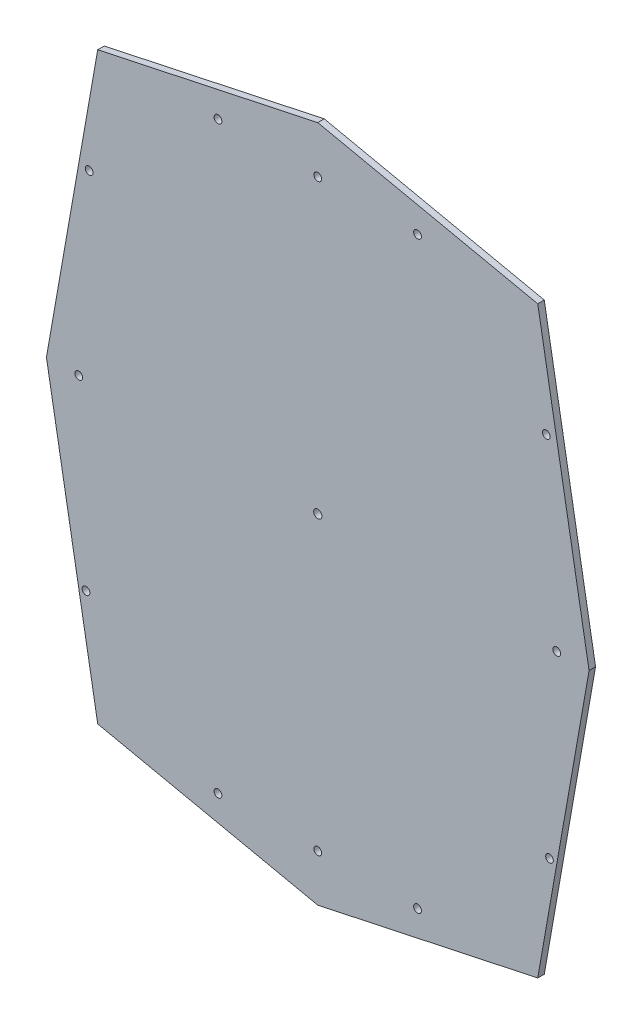
SolidWorks part; units mm, degrees
ref_plane "Front Plane" through (0, 0, 0) normal (0, 0, 1) x (1, 0, 0)
ref_plane "Top Plane" through (0, 0, 0) normal (0, 1, 0) x (1, 0, 0)
ref_plane "Right Plane" through (0, 0, 0) normal (1, 0, 0) x (0, 0, -1)
sketch "Sketch1" plane through (0, 0, -617.8603) normal (0, 0, 1) x (1, 0, 0)
  line L0 (-107.5, 142.6399) -> (-132.5632, 0)
  line L10 (-107.5, -142.6399) -> (-132.5632, 0)
  line L13 (0, 188.5) -> (0, 142.6399) construction
  line L14 (-130, 89.4108) -> (-111.25, 89.4108) construction
  line L15 (-141, 0) -> (-116.7559, 0) construction
  line L18 (107.5, -142.6399) -> (132.5632, 0)
  line L19 (107.5, 142.6399) -> (132.5632, 0)
  line L24 (-107.5, 142.6399) -> (0, 165.5699)
  line L25 (0, 165.5699) -> (107.5, 142.6399)
  line L27 (-184.8413, 0) -> (193.3832, 0) construction
  line L33 (0, -165.5699) -> (107.5, -142.6399)
  line L34 (-107.5, -142.6399) -> (0, -165.5699)
  circle A25 centre (48.75, -142.6399) radius 1.8987
  circle A26 centre (0, -142.6399) radius 1.8987
  circle A27 centre (-48.75, -142.6399) radius 1.8987
  circle A28 centre (-113.2269, -89.1534) radius 1.8987
  circle A29 centre (-116.75, 0.1657) radius 1.8987
  circle A30 centre (-111.6902, 89.4108) radius 1.8987
  circle A31 centre (111.6902, 89.4108) radius 1.8987
  circle A32 centre (116.75, 0.1657) radius 1.8986
  circle A33 centre (113.2269, -89.1534) radius 1.8692
  circle A37 centre (48.75, 142.6399) radius 1.8987
  circle A38 centre (0, 142.6399) radius 1.8987
  circle A39 centre (-48.75, 142.6399) radius 1.8987
  point P0 (0, 0)
  point P16 (0, -142.6399)
  point P17 (0, 142.6399)
extrude "MainBody" add sketch "Sketch1" along normal blind 3.175
hole_wizard "#10-32 Tapped Hole1" positions "Sketch2" profile "Sketch3" tap size "#10-32" standard "ANSI Inch" end condition up to next
sketch "Sketch2" plane through (0, 0, -614.6853) normal (0, 0, 1) x (1, 0, 0)
  point P0 (0, 0)
sketch "Sketch3" plane through (0, 0, -614.6853) normal (1, 0, 0) x (0, -1, 0)
  line L0 (0, 0) -> (0, 3.175)
  line L1 (0, 3.175) -> (2.0193, 3.175)
  line L2 (2.0193, 3.175) -> (2.0193, 0)
  line L5 (2.0193, 0) -> (0, 0)
  line L11 (0, -6.35) -> (0, 107.95) construction
  dimension "Thru Tap Drill Dia." = 4.0386
  dimension "Thru Tap Drill Depth" = 3.175
cosmetic thread "Hole Thread1" parameters "D2"=4.826
